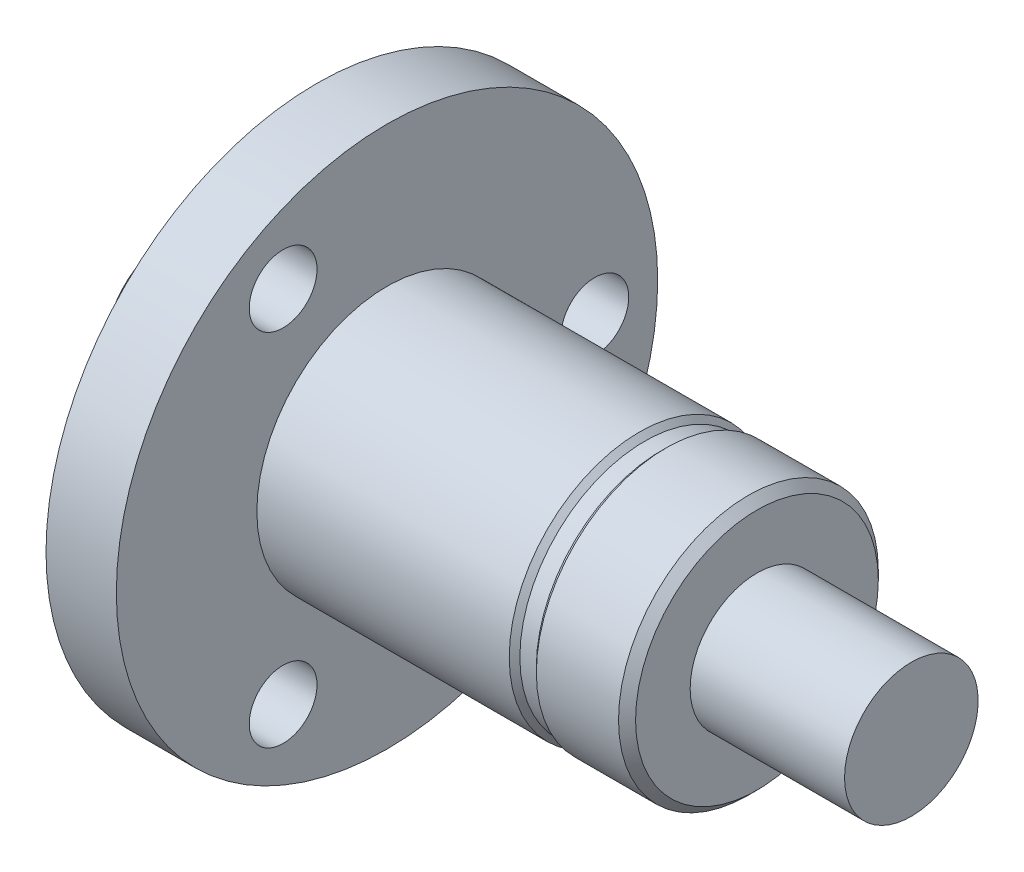
SolidWorks part; units mm, degrees
ref_plane "Front Plane" through (0, 0, 0) normal (0, 0, 1) x (1, 0, 0)
ref_plane "Top Plane" through (0, 0, 0) normal (0, 1, 0) x (1, 0, 0)
ref_plane "Right Plane" through (0, 0, 0) normal (1, 0, 0) x (0, 0, -1)
sketch "Sketch1" plane through (0, 0, 0) normal (0, 0, 1) x (1, 0, 0)
  line L1 (17.3559, 6.095) -> (17.3559, 0)
  line L2 (0, 6.1078) -> (0, 12.7)
  line L3 (0, 12.7) -> (-3.3, 12.7)
  line L4 (-3.3, 12.7) -> (-3.3, 0)
  line L5 (-3.3, 0) -> (17.3559, 0)
  line L6 (-10.1, 3.1336) -> (-10.1, 0)
  line L7 (-10.1, 3.1336) -> (24.6, 3.1336)
  line L8 (24.6, 0) -> (24.6, 3.1336)
  line L9 (-10.1, 0) -> (24.6, 0)
  line L10 (0, 6.1078) -> (12.2421, 6.1078)
  line L11 (12.2421, 6.1078) -> (12.2421, 5.8595)
  line L12 (12.2421, 5.8595) -> (12.7, 5.8595)
  line L13 (12.7, 5.8595) -> (12.7, 6.095)
  line L14 (12.7, 6.095) -> (17.3559, 6.095)
  dimension "D1" = 3.3
  dimension "D3" = 6.095
  dimension "D4" = 12.7
  dimension "D5" = 0
  dimension "D6" = 0
  dimension "D7" = 6.8
  dimension "D8" = 34.7
  dimension "D9" = 11.9
revolve "Revolve1" add sketch "Sketch1" angle 360 about L5 region at (4.7407, 5.8712, 0) region at (20.978, 1.5668, 0) region at (7.028, 1.5668, 0) region at (-6.7, 1.5668, 0)
sketch "Sketch2" plane through (0, 0, 0) normal (1, 0, 0) x (0, 0, -1)
  circle A0 centre (9.75, 0) radius 1.59
  dimension "D1" = 3.18
  dimension "D2" = 9.75
extrude "Cut-Extrude1" cut sketch "Sketch2" against normal blind 10
pattern_circular "CirPattern1" count 3 over 360 about axis through (-3.3, 0, 0) along (-1, 0, 0) of "Cut-Extrude1"
chamfer "Chamfer1" distance 0.4 angle 45 3 edges at (17.3559, 0, 6.095) (12.7, 0, 6.095) (12.2421, 0, 6.1078)
